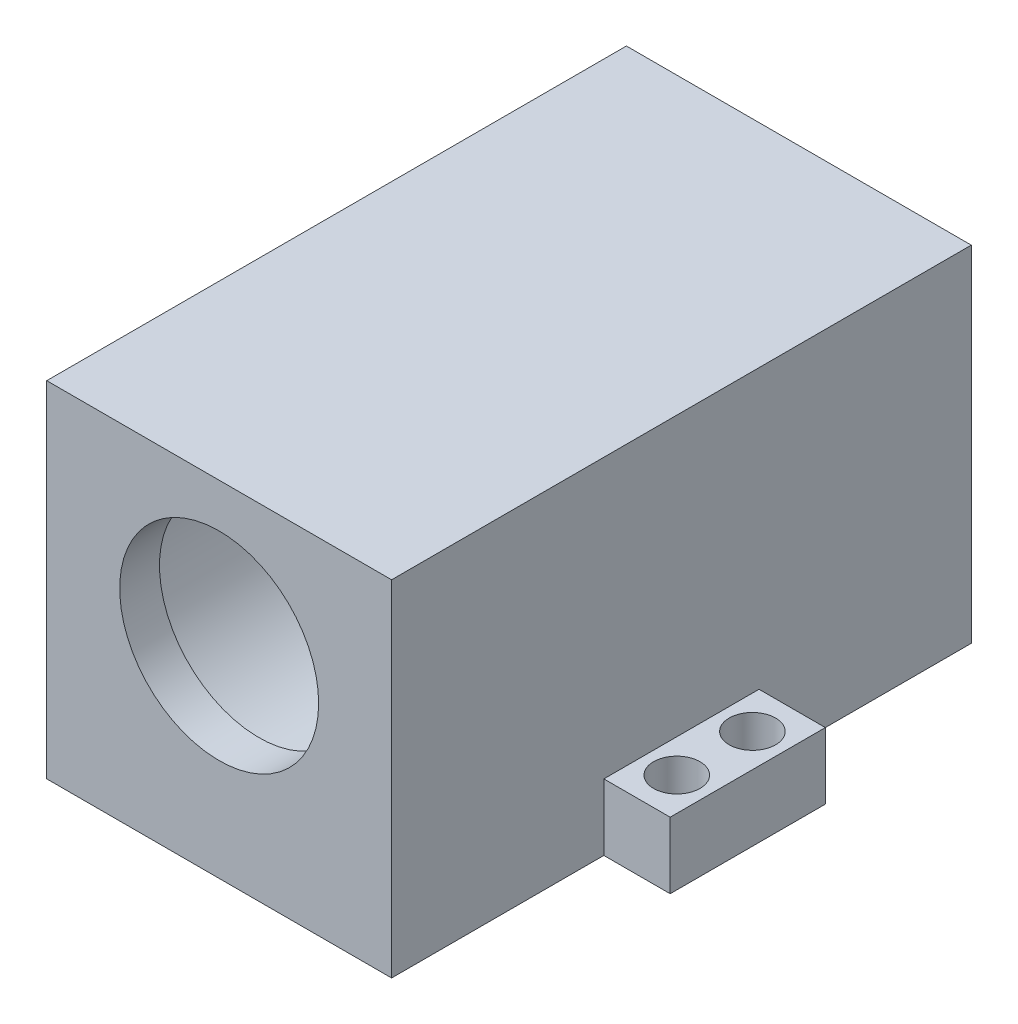
SolidWorks part; units mm, degrees
ref_plane "Plan de face" through (0, 0, 0) normal (0, 0, 1) x (1, 0, 0)
ref_plane "Plan de dessus" through (0, 0, 0) normal (0, 1, 0) x (1, 0, 0)
ref_plane "Plan de droite" through (0, 0, 0) normal (1, 0, 0) x (0, 0, -1)
sketch "Esquisse1" plane through (0, 0, 0) normal (0, 0, 1) x (1, 0, 0)
  line L1 (13, 10.81) -> (-13, 10.81)
  line L2 (13, 10.81) -> (13, -15.19)
  line L3 (13, -15.19) -> (-13, -15.19)
  line L4 (-13, 10.81) -> (-13, -15.19)
  circle A0 centre (0, 0) radius 10.6
  point P3 (0, 10.6)
  point P8 (0, -10.6)
  point P9 (0, -15.19)
  dimension "D1" = 21.2
  dimension "D2" = 13
  dimension "D3" = 13
  dimension "D4" = 15.19
  dimension "D5" = 4.59
  dimension "D6" = 26
extrude "Boss.-Extru.1" add sketch "Esquisse1" along normal blind 40.7
sketch "Esquisse7" plane through (0, 0, 40.7) normal (0, 0, 1) x (1, 0, 0)
  line L1 (-13, 10.81) -> (13, 10.81)
  line L2 (-13, 10.81) -> (-13, -15.19)
  line L3 (-13, -15.19) -> (13, -15.19)
  line L4 (13, 10.81) -> (13, -15.19)
  circle A0 centre (0, 0) radius 7.5
  dimension "D1" = 15
extrude "Boss.-Extru.5" add sketch "Esquisse7" along normal blind 3
sketch "Esquisse8" plane through (0, 0, 0) normal (0, 0, -1) x (-1, 0, 0)
  line L0 (13, 10.81) -> (13, -15.19) construction
  line L1 (-13, -15.19) -> (13, -15.19)
  line L2 (-13, -15.19) -> (-13, -11.19)
  line L3 (-13, -11.19) -> (13, -11.19)
  line L4 (13, -15.19) -> (13, -11.19)
  dimension "D1" = 4
sketch "Esquisse9" plane through (-13, 0, 0) normal (-1, 0, 0) x (0, 0, 1)
  line L0 (43.7, -15.19) -> (0, -15.19) construction
  line L1 (16, -15.19) -> (27.7, -15.19)
  line L2 (16, -15.19) -> (16, -10.19)
  line L3 (16, -10.19) -> (27.7, -10.19)
  line L4 (27.7, -15.19) -> (27.7, -10.19)
  line L5 (0, -15.19) -> (0, -11.19) construction
  line L6 (43.7, 10.81) -> (43.7, -15.19) construction
  dimension "D1" = 5
  dimension "D2" = 16
  dimension "D3" = 16
extrude "Boss.-Extru.6" add sketch "Esquisse9" along normal blind 5 contours L2 L1 L4 L3
sketch "Esquisse11" plane through (0, -10.19, 0) normal (0, 1, 0) x (1, 0, 0)
  line L1 (-18, -27.7) -> (-13, -27.7) construction
  line L2 (-18, -16) -> (-13, -16) construction
  circle A0 centre (-15.45, -19) radius 1.75
  circle A1 centre (-15.45, -24.7) radius 1.75
  point P0 (-13, -16)
  point P1 (-13, -27.7)
  point P3 (-18, -27.7)
  point P5 (-18, -16)
  point P9 (-15.45, -19)
  point P10 (-15.45, -24.7)
  dimension "D1" = 3.5
  dimension "D2" = 3.5
  dimension "D5" = 3
  dimension "D6" = 3
extrude "Enlèv. mat.-Extru.1" cut sketch "Esquisse11" against normal through all contours A0 | A1
sketch "Esquisse12" plane through (0, 10.81, 0) normal (0, 1, 0) x (1, 0, 0)
  line L0 (0, 0) -> (0, -55.8192) construction
ref_axis "Axe1" through (0, 10.81, 0) along (0, 0, 1)
sketch "Esquisse17" plane through (13, 0, 0) normal (1, 0, 0) x (0, 0, -1)
  line L0 (-43.7, -15.19) -> (0, -15.19) construction
  line L1 (-27.7, -15.19) -> (-16, -15.19)
  line L2 (-27.7, -15.19) -> (-27.7, -10.19)
  line L3 (-27.7, -10.19) -> (-16, -10.19)
  line L4 (-16, -15.19) -> (-16, -10.19)
  line L5 (-43.7, -15.19) -> (-43.7, 10.81) construction
  line L6 (0, -15.19) -> (0, -11.19) construction
  dimension "D1" = 16
  dimension "D2" = 16
  dimension "D3" = 5
extrude "Boss.-Extru.7" add sketch "Esquisse17" along normal blind 5
sketch "Esquisse18" plane through (0, -10.19, 0) normal (0, 1, 0) x (1, 0, 0)
  line L0 (-15.45, -24.7) -> (15.5, -24.7) construction
  line L1 (-15.45, -19) -> (15.5, -19) construction
  line L2 (15.5, -27.7) -> (15.5, -16) construction
  line L5 (18, -27.7) -> (13, -27.7) construction
  line L6 (18, -16) -> (13, -16) construction
  circle A0 centre (15.5, -24.7) radius 1.75
  circle A2 centre (15.5, -19) radius 1.75
  dimension "D1" = 3.5
  dimension "D2" = 3.5
extrude "Enlèv. mat.-Extru.2" cut sketch "Esquisse18" against normal through all
